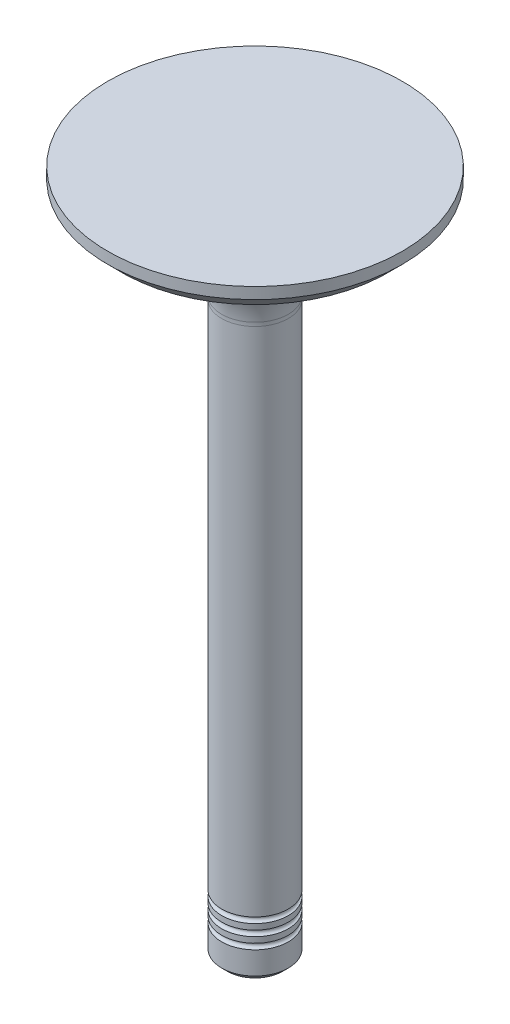
SolidWorks part; units mm, degrees
material "Silchrome I"
ref_plane "Front Plane" through (0, 0, 0) normal (0, 0, 1) x (1, 0, 0)
ref_plane "Top Plane" through (0, 0, 0) normal (0, 1, 0) x (1, 0, 0)
ref_plane "Right Plane" through (0, 0, 0) normal (1, 0, 0) x (0, 0, -1)
sketch "Sketch1" plane through (0, 0, 0) normal (0, 0, 1) x (1, 0, 0)
  line L0 (0, 224.083) -> (0, 103.823) construction
  line L1 (0, 224.083) -> (-25.92, 224.083)
  line L2 (-25.92, 224.083) -> (-25.92, 222.083)
  line L3 (-25.92, 222.083) -> (-23.328, 219.491)
  line L5 (-5.85, 204.053) -> (-5.85, 103.823)
  line L6 (-5.85, 103.823) -> (0, 103.823)
  line L7 (0, 224.083) -> (0, 103.823)
  arc A3 (-23.328, 219.491) -> (-5.85, 204.053) centre (-21.9947, 203.3877) cw
  dimension "D1" = 25.92
  dimension "D2" = 45
  dimension "D4" = 5.85
  dimension "D5" = 18.03
  dimension "D7" = 120.26
  dimension "D3" = 2.592
  dimension "D6" = 2
revolve "Revolve1" add sketch "Sketch1" angle 360 about L0
fillet "Fillet1" radius 10 1 edges at (-5.85, 204.053, 0)
chamfer "Chamfer1" distance 1 angle 45 1 edges at (-5.85, 103.823, 0)
sketch "Sketch5" plane through (0, 0, 0) normal (1, 0, 0) x (0, 0, -1)
  line L1 (-5.85, 203.7983) -> (-5.85, 104.823) construction
  line L3 (-7.48, 111.823) -> (-5.85, 111.823)
  line L4 (0, 203.7983) -> (0, 104.823) construction
  line L5 (5.85, 203.7983) -> (-5.85, 203.7983) construction
  line L6 (5.85, 104.823) -> (-5.85, 104.823) construction
  line L7 (-7.48, 110.823) -> (-5.85, 110.823)
  line L8 (-7.48, 108.823) -> (-5.85, 108.823)
  line L9 (-7.48, 108.823) -> (-7.48, 109.823)
  line L10 (-7.48, 109.823) -> (-5.85, 109.823)
  line L12 (-7.48, 110.823) -> (-7.48, 111.823)
  line L13 (-7.48, 113.823) -> (-5.85, 113.823)
  line L14 (-7.48, 112.823) -> (-5.85, 112.823)
  line L15 (-7.48, 112.823) -> (-7.48, 113.823)
  arc A0 (-5.85, 108.823) -> (-5.85, 109.823) centre (-5.85, 109.323) ccw
  arc A1 (-5.85, 110.823) -> (-5.85, 111.823) centre (-5.85, 111.323) ccw
  arc A2 (-5.85, 112.823) -> (-5.85, 113.823) centre (-5.85, 113.323) ccw
  point P10 (-6.85, 109.323)
  dimension "D1" = 1
  dimension "D2" = 1
  dimension "D6" = 4
  dimension "D7" = 6
  dimension "D3" = 3
revolve "Cut-Revolve2" cut sketch "Sketch5" angle 360 about L4
sketch "Sketch6" plane through (0, 0, 0) normal (0, 0, 1) x (1, 0, 0)
  line L0 (0, 224.083) -> (0, 93.6363) construction
  line L1 (25.92, 224.083) -> (-25.92, 224.083) construction
ref_plane "Mating Plane" through (0, 222.083, 0) normal (0, 1, 0) x (1, 0, 0)
equation "\"Valve Diameter\"= 51.84mm"
equation "\"Seat Angle Beta\"= 45deg"
equation "\"Seat Diameter\"= 46.656mm"
equation "\"Stem Diameter\"= 12.96mm"
equation "\"Max Lift\"= 18.03mm"
equation "\"Seat Width\"= 2.592mm"
equation "\"D1@Sketch1\"=\"Valve Diameter\"/2"
equation "\"D2@Sketch1\"=\"Seat Angle Beta\""
equation "\"D5@Sketch1\"=\"Max Lift\""
equation "\"Head Thickness\"= 2mm"
equation "\"Overall Length\"= 120.26mm"
equation "\"D7@Sketch1\"=\"Overall Length\""
equation "\"D3@Sketch1\"=\"Seat Width\""
equation "\"D6@Sketch1\"=\"Head Thickness\""
